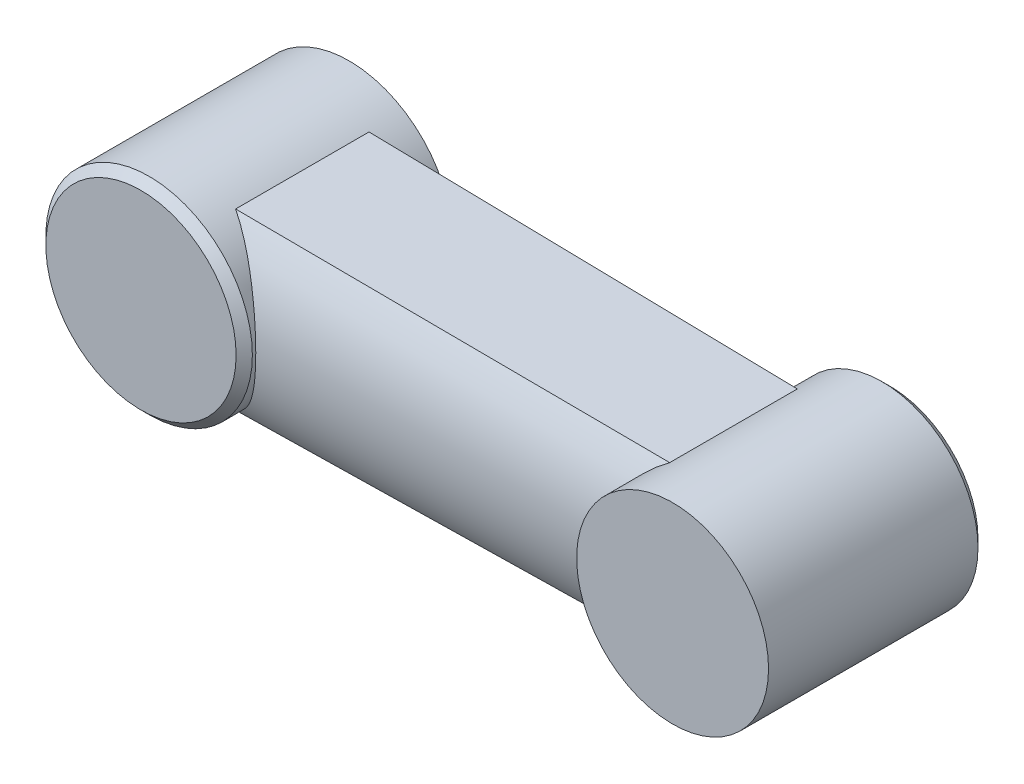
SolidWorks part; units mm, degrees
ref_plane "Front Plane" through (0, 0, 0) normal (0, 0, 1) x (1, 0, 0)
ref_plane "Top Plane" through (0, 0, 0) normal (0, 1, 0) x (1, 0, 0)
ref_plane "Right Plane" through (0, 0, 0) normal (1, 0, 0) x (0, 0, -1)
sketch "Sketch1" plane through (0, 0, 0) normal (0, 0, 1) x (1, 0, 0)
  circle A0 centre (0, 0) radius 63.5
  dimension "D1" = 127
extrude "Boss-Extrude1" add sketch "Sketch1" along normal blind 64 and the other way blind 64
chamfer "Chamfer1" distance 5 angle 45 1 edges at (63.5, 0, 64)
ref_plane "Plane2" through (63.5, 0, 0) normal (1, 0, 0) x (0, 0, -1)
ref_plane "Plane1" through (271.2, 0, 0) normal (1, 0, 0) x (0, 0, -1)
ref_plane "Plane3" through (330.2, 0, 0) normal (1, 0, 0) x (0, 0, -1)
ref_plane "Plane4" through (0, 0, 0) normal (0, 0, 1) x (1, 0, 0)
sketch "Sketch6" plane through (0, 0, 0) normal (-1, 0, 0) x (0, 0, 1)
  line L0 (-57.7088, 0) -> (57.7088, 0) construction
  line L6 (40.1204, -54) -> (-42.3796, -54)
  line L7 (-42.3796, 54) -> (40.1204, 54)
  arc A5 (-42.3796, 54) -> (-42.3796, -54) centre (45.0683, 0) ccw
  arc A6 (40.1204, 54) -> (40.1204, -54) centre (-33.9807, 0) cw
sketch "Sketch7" plane through (330.2, 0, 59) normal (-1, 0, 0) x (0, 0, 1)
  line L0 (-21.0035, -49.884) -> (-99.0528, -49.884)
  line L6 (-99.0528, 49.884) -> (-21.0035, 49.884)
  line L7 (-112.5928, 0) -> (-5.4072, 0) construction
  arc A9 (-99.0528, 49.884) -> (-99.0528, -49.884) centre (-13.9317, 0) ccw
  arc A10 (-21.0035, 49.884) -> (-21.0035, -49.884) centre (-92.9807, 0) cw
loft "Loft1" add profiles "Sketch6", "Sketch7" start constraint default end constraint default connector at (0, 54, 40.1204) connector at (330.2, 49.884, 37.9965)
sketch "Sketch9" plane through (0, 0, 0) normal (0, 0, 1) x (1, 0, 0)
  line L0 (330.2, -49.884) -> (330.2, 49.884) construction
  circle A0 centre (330.2, 0) radius 59
  dimension "D1" = 118
extrude "Boss-Extrude2" add sketch "Sketch9" along normal blind 67.3 and the other way blind 66.5
chamfer "Chamfer2" distance 5 angle 45 1 edges at (389.2, 0, -66.5)
ref_axis "Axis1" through (0, 0, 59) along (0, 0, -1)
ref_point "Point1"
